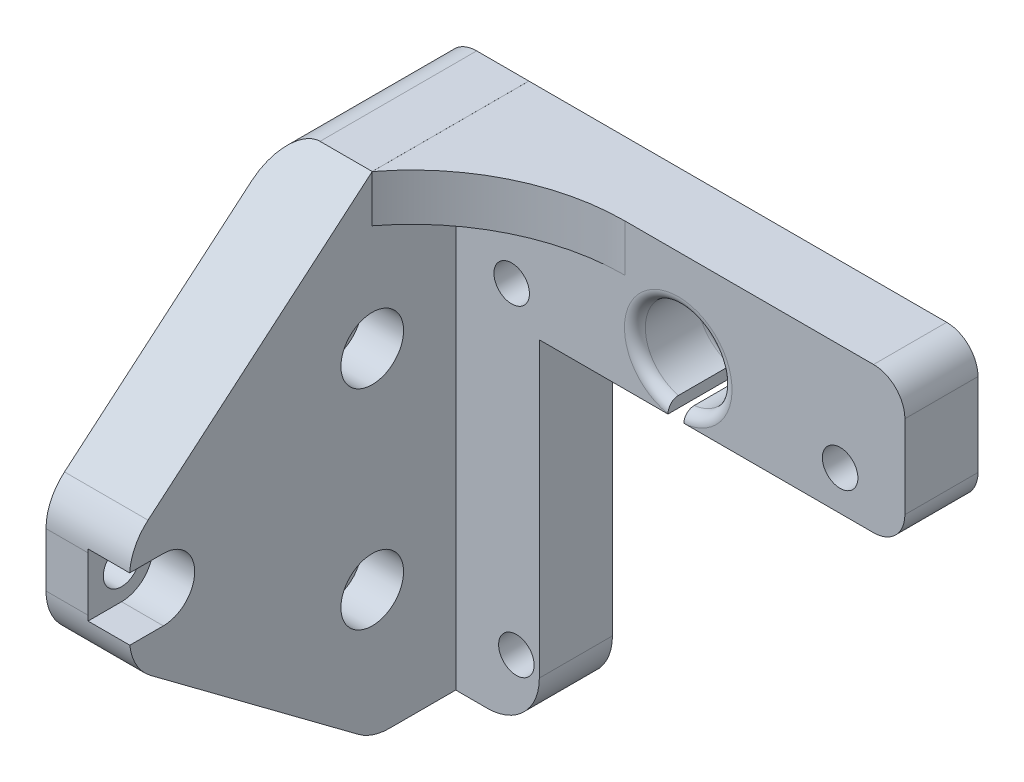
SolidWorks part; units mm, degrees
material "ABS"
ref_plane "Front Plane" through (0, 0, 0) normal (0, 0, 1) x (1, 0, 0)
ref_plane "Top Plane" through (0, 0, 0) normal (0, 1, 0) x (1, 0, 0)
ref_plane "Right Plane" through (0, 0, 0) normal (1, 0, 0) x (0, 0, -1)
ref_plane "Plane5" through (60, 0, 0) normal (1, 0, 0) x (0, 0, -1)
sketch "Sketch50" plane through (60, 0, 0) normal (1, 0, 0) x (0, 0, -1)
  line L0 (-38.2349, -28) -> (-38.2349, -38)
  line L1 (0, -55.3249) -> (-15, -55.3249)
  line L2 (0, -8.3249) -> (-15, -8.3249)
  line L4 (0, -55.3249) -> (0, -8.3249)
  line L5 (-15, -2.0171) -> (-15, -57.8143) construction
  line L9 (-38.2349, -28) -> (-15, -8.3249)
  line L10 (-38.2349, -38) -> (-15, -55.3249)
  circle A0 centre (-35, -33) radius 1.75
  circle A1 centre (-15, -23) radius 1.75
  circle A2 centre (-15, -43) radius 1.75
  dimension "D1" = 3.5
  dimension "D2" = 3.5
  dimension "D3" = 3.5
  dimension "D4" = 20
  dimension "D5" = 20
  dimension "D6" = 47
  dimension "D7" = 15
  dimension "D8" = 10
extrude "Extrude1" add sketch "Sketch50" along normal blind 8 separate body
sketch "Sketch52" plane through (0, 0, 0) normal (0, 0, -1) x (-1, 0, 0)
  line L0 (-60.0211, -55.3284) -> (-60.0211, -8.3284)
  line L1 (-111, -8.3284) -> (-111, -22.2806)
  line L2 (-60.0211, -8.3284) -> (-111, -8.3284)
  line L3 (-76, -22.2806) -> (-111, -22.2806)
  line L4 (-60.0211, -55.3284) -> (-76, -55.3284)
  line L5 (-76, -55.3249) -> (-76, -8.3249)
  line L6 (-76, -55.3284) -> (-76, -22.2806)
  circle A0 centre (-89.3, -17.2) radius 4.15
  circle A1 centre (-73.3515, -18.9313) radius 1.7
  circle A2 centre (-104.8, -18.5) radius 1.7
  circle A3 centre (-73.8015, -49.5086) radius 1.7
  point P3 (-113, -87.5802)
  point P9 (-74.0211, -54.9585)
  point P10 (-74.0211, -7.7617)
  dimension "D2" = 47
  dimension "D4" = 3.4
  dimension "D3" = 8.3
  dimension "D1" = 8
extrude "Extrude2" add sketch "Sketch52" against normal blind 7
fillet "Fillet1" radius 3 2 edges at (111, -22.2806, 3.5) (111, -8.3284, 3.5)
fillet "Fillet2" radius 5 1 edges at (76, -55.3284, 3.5)
sketch "Sketch54" plane through (0, -8.3284, 0) normal (0, 1, 0) x (1, 0, 0)
  line L0 (68, -7) -> (108, -7) construction
  line L1 (68, -15) -> (68, -7)
  line L2 (68, -15) -> (68, -38.2349) construction
  line L3 (68, 0) -> (68, -15) construction
  line L4 (68, -7) -> (84.1795, -7)
  arc A0 (84.1795, -7) -> (68, -15) centre (84.1795, -27.3609) ccw
extrude "Extrude3" add sketch "Sketch54" against normal blind 4.5
fillet "Fillet4" radius 5 3 edges at (64, -28, 38.2349) (64, -38, 38.2349) (64, -55.3249, 15)
fillet "Fillet5" radius 3 1 edges at (60, -8.3249, 7.5)
sketch "Sketch55" plane through (68, 0, 0) normal (1, 0, 0) x (0, 0, -1)
  line L0 (-35, -30) -> (-38.7879, -30)
  line L1 (-38.7879, -30) -> (-38.7879, -36)
  line L2 (-35, -36) -> (-38.7879, -36)
  arc A0 (-35, -36) -> (-35, -30) centre (-35, -33) ccw
  circle A1 centre (-15, -23) radius 3
  circle A2 centre (-15, -43) radius 3
  dimension "D1" = 6
  dimension "D2" = 6
  dimension "D3" = 6
extrude "Cut-Extrude3" cut sketch "Sketch55" against normal blind 4
sketch "Sketch56" plane through (0, 0, 0) normal (0, 0, -1) x (-1, 0, 0)
  line L0 (-108, -22.2806) -> (-76, -22.2806) construction
  line L1 (-89.3173, -23.6005) -> (-88.3204, -23.6005)
  line L2 (-89.3173, -23.6005) -> (-89.3173, -20.9607)
  line L3 (-89.3173, -20.9607) -> (-88.3204, -20.9607)
  line L4 (-88.3204, -23.6005) -> (-88.3204, -20.9607)
  line L5 (-89.3173, -23.6005) -> (-88.3204, -20.9607) construction
  line L6 (-89.3173, -20.9607) -> (-88.3204, -23.6005) construction
  point P0 (-88.8189, -22.2806)
fillet "Fillet9" radius 1 1 edges at (89.3, -13.05, 0)
fillet "Fillet10" radius 1 1 edges at (89.3, -13.05, 7)
sketch "Sketch57" plane through (0, -22.2806, 0) normal (0, -1, 0) x (1, 0, 0)
  line L0 (88.8276, 7.5275) -> (89.8276, 7.5275)
  line L2 (89.8276, -0.6284) -> (89.8276, 7.5275)
  line L3 (88.8276, -0.6284) -> (88.8276, 7.5275)
  line L4 (88.8276, -0.6284) -> (89.8276, -0.6284)
extrude "Extrude4" cut sketch "Sketch57" against normal blind 4
extrude "Cut-Extrude4" cut sketch "Sketch56" against normal up to surface (7 mm away) up to face at (84.4186, -28.299, 7)
